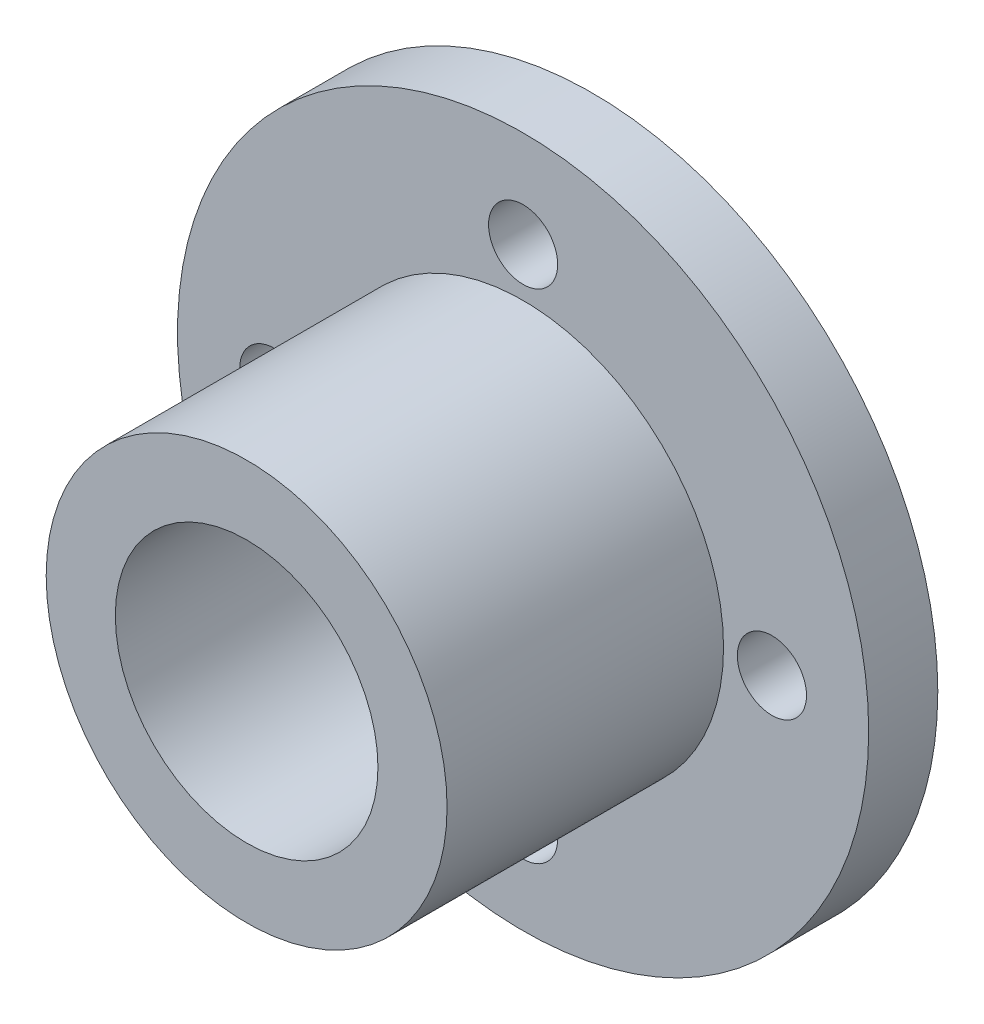
SolidWorks part; units mm, degrees
material "Plain Carbon Steel"
ref_plane "Front" through (0, 0, 0) normal (0, 0, 1) x (1, 0, 0)
ref_plane "Top" through (0, 0, 0) normal (0, 1, 0) x (1, 0, 0)
ref_plane "Right" through (0, 0, 0) normal (1, 0, 0) x (0, 0, -1)
sketch "Sketch1" plane through (0, 0, 0) normal (0, 0, 1) x (1, 0, 0)
  circle A0 centre (0, 0) radius 25
  dimension "D1" = 50
extrude "Boss-Extrude1" add sketch "Sketch1" along normal blind 5
sketch "Sketch2" plane through (0, 0, 5) normal (0, 0, 1) x (1, 0, 0)
  circle A0 centre (0, 0) radius 14.5
  circle A1 centre (0, 0) radius 9.5
  dimension "D1" = 29
  dimension "D2" = 19
extrude "Boss-Extrude2" add sketch "Sketch2" along normal blind 20
sketch "Sketch3" plane through (0, 0, 0) normal (0, 0, -1) x (-1, 0, 0)
  circle A0 centre (0, 0) radius 9.5
  dimension "D1" = 19
extrude "Cut-Extrude1" cut sketch "Sketch3" against normal blind 15
sketch "Sketch4" plane through (0, 0, 0) normal (0, 0, -1) x (-1, 0, 0)
  circle A0 centre (0, 18) radius 2.5
  circle A1 centre (18, 0) radius 2.5
  circle A2 centre (0, -18) radius 2.5
  circle A3 centre (-18, 0) radius 2.5
  point P12 (0, 0)
  dimension "D1" = 5
  dimension "D2" = 18
  dimension "D3" = 4
extrude "Cut-Extrude2" cut sketch "Sketch4" against normal blind 10
